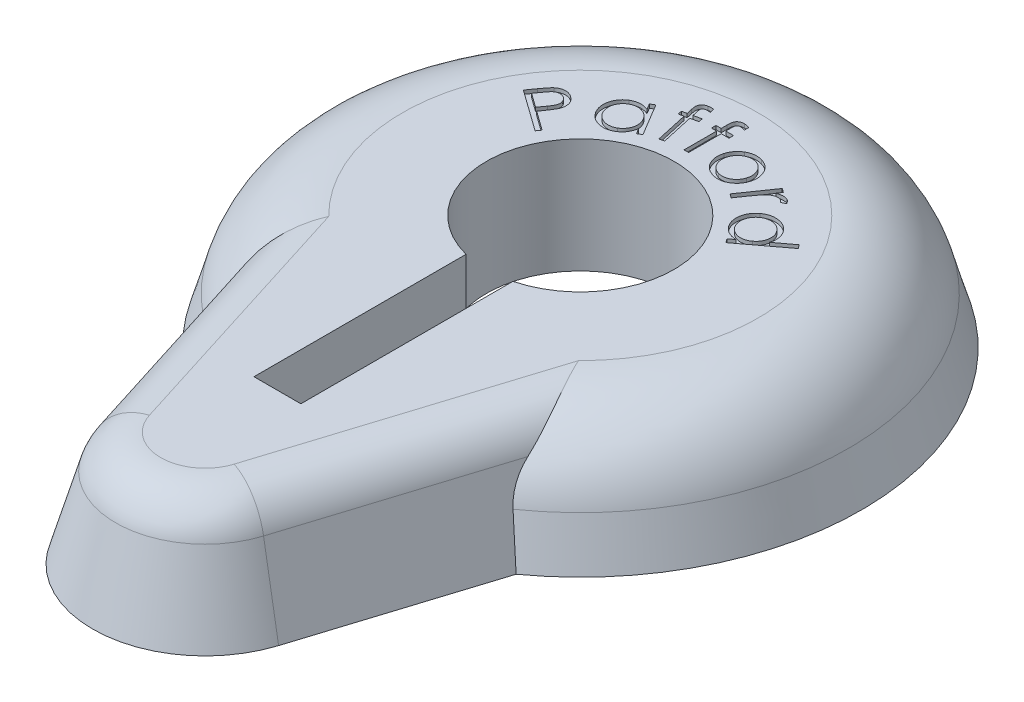
SolidWorks part; units mm, degrees
ref_plane "Front Plane" through (0, 0, 0) normal (0, 0, 1) x (1, 0, 0)
ref_plane "Top Plane" through (0, 0, 0) normal (0, 1, 0) x (1, 0, 0)
ref_plane "Right Plane" through (0, 0, 0) normal (1, 0, 0) x (0, 0, -1)
sketch "Sketch1" plane through (0, 0, 0) normal (0, 1, 0) x (1, 0, 0)
  line L0 (0, 0) -> (0, 48.0738) construction
  line L1 (-14.5346, -8.0215) -> (-22.2438, 16.4286)
  line L2 (14.5346, -8.0215) -> (22.2438, 16.4286)
  arc A0 (-14.5346, -8.0215) -> (14.5346, -8.0215) centre (0, -3.4388) ccw
  arc A1 (-22.2438, 16.4286) -> (22.2438, 16.4286) centre (0, 47.3612) cw
  dimension "D1" = 38.1
  dimension "D2" = 15.24
  dimension "D3" = 50.8
  dimension "D4" = 35
extrude "Boss-Extrude1" add sketch "Sketch1" along normal blind 15.494 draft 16
fillet "Fillet2" radius 6.35 3 edges at (-14.3818, 15.494, -6.2683) (0, 15.494, 14.236) (14.3818, 15.494, -6.2683)
fillet "Fillet3" radius 12.7 1 edges at (0, 15.494, -81.0184)
sketch "Sketch2" plane through (0, 15.494, 0) normal (0, 1, 0) x (1, 0, 0)
  circle A0 centre (0, 47.3612) radius 12.7
  dimension "D1" = 25.4
extrude "Cut-Extrude1" cut sketch "Sketch2" against normal through all both and the other way through all
sketch "Sketch3" plane through (0, 15.494, 0) normal (0, 1, 0) x (1, 0, 0)
  line L0 (0, 0) -> (0, 29.1069) construction
  line L5 (0, 6.35) -> (0, 0) construction
  line L14 (-3.175, 57.15) -> (3.175, 57.15)
  line L15 (-3.175, 57.15) -> (-3.175, 6.35)
  line L16 (-3.175, 6.35) -> (3.175, 6.35)
  line L17 (3.175, 57.15) -> (3.175, 6.35)
  point P8 (0, -0.9558)
  dimension "D1" = 6.35
  dimension "D2" = 50.8
  dimension "D3" = 6.35
extrude "Cut-Extrude3" cut sketch "Sketch3" against normal blind 6.35
sketch "Sketch5" plane through (0, 15.494, 0) normal (0, 1, 0) x (1, 0, 0)
  text T0 "Pafford" font "Century Gothic" height in points 26
extrude "Cut-Extrude5" cut sketch "Sketch5" against normal blind 0.508
